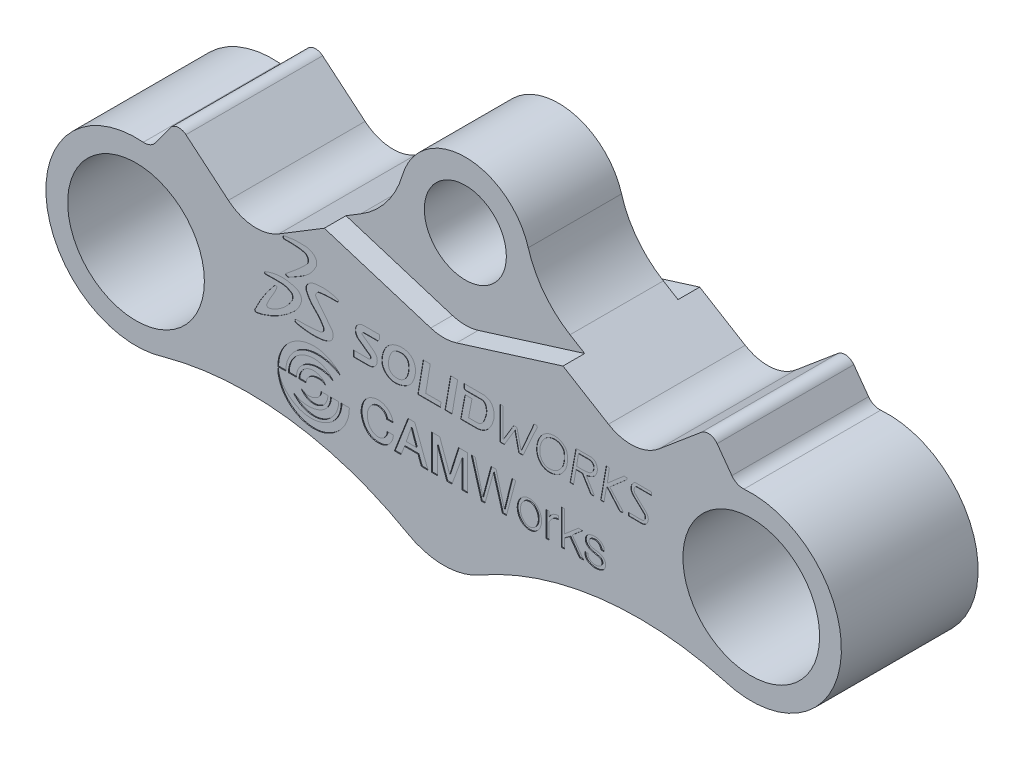
SolidWorks part; units mm, degrees
material "6061-T6 (SS)"
ref_plane "Front Plane" through (0, 0, 0) normal (0, 0, 1) x (1, 0, 0)
ref_plane "Top Plane" through (0, 0, 0) normal (0, 1, 0) x (1, 0, 0)
ref_plane "Right Plane" through (0, 0, 0) normal (1, 0, 0) x (0, 0, -1)
sketch "Sketch1" plane through (0, 0, 0) normal (0, 0, 1) x (1, 0, 0)
  line L0 (0, 0) -> (45, 7.9347) construction
  line L1 (0, 0) -> (0, 30) construction
  line L2 (0, 0) -> (0, -25.1431) construction
  line L3 (0, 0) -> (113.4618, 0) construction
  line L4 (45, 7.9347) -> (34.3559, 20.6199) construction
  line L5 (45, 7.9347) -> (45, 35.6707) construction
  line L11 (39.0067, 26.2508) -> (42.1595, 21.8988)
  line L13 (39.0067, 26.2508) -> (28.0029, 17.0175)
  line L14 (-45, 7.9347) -> (-34.3559, 20.6199) construction
  line L17 (28.0029, 17.0175) -> (15.3139, 24.7315)
  line L18 (0, 0) -> (-45, 7.9347) construction
  line L19 (-28.0029, 17.0175) -> (-15.3139, 24.7315)
  line L22 (-39.0067, 26.2508) -> (-28.0029, 17.0175)
  line L24 (-39.0067, 26.2508) -> (-42.1595, 21.8988)
  circle A0 centre (0, 30) radius 8 construction
  circle A2 centre (0, 0) radius 5.5562 construction
  circle A3 centre (45, 7.9347) radius 10 construction
  arc A5 (42.1595, 21.8988) -> (43.9399, 21.0787) centre (43.7791, 23.0722) ccw
  circle A7 centre (0, 30) radius 9.5875 construction
  arc A8 (10.5563, 0) -> (10.3959, 1.8331) centre (0, 0) ccw
  arc A9 (5.2476, -9.1596) -> (41.0161, -4.6357) centre (28.5656, -49.8611) cw
  arc A10 (9.2011, 32.6943) -> (-9.2011, 32.6943) centre (0, 30) ccw
  arc A11 (15.3139, 24.7315) -> (9.2011, 32.6943) centre (22.5268, 36.5963) cw
  arc A12 (41.0161, -4.6357) -> (43.9399, 21.0787) centre (45, 7.9347) ccw
  circle A13 centre (0, 0) radius 10.5563 construction
  arc A14 (-41.0161, -4.6357) -> (-43.9399, 21.0787) centre (-45, 7.9347) cw
  arc A15 (-15.3139, 24.7315) -> (-9.2011, 32.6943) centre (-22.5268, 36.5963) ccw
  arc A16 (-5.2476, -9.1596) -> (-41.0161, -4.6357) centre (-28.5656, -49.8611) ccw
  arc A19 (-42.1595, 21.8988) -> (-43.9399, 21.0787) centre (-43.7791, 23.0722) cw
  circle A21 centre (-45, 7.9347) radius 10 construction
  arc A22 (-5.2476, -9.1596) -> (5.2476, -9.1596) centre (0, 0) ccw
  point P26 (9.1088, 28.1848)
  point P35 (9.8679, 3.0169)
  dimension "D1" = 16
  dimension "D3" = 11.1125
  dimension "D6" = 20
  dimension "D12" = 2
  dimension "D4" = 45
  dimension "D5" = 30
  dimension "D7" = 10
  dimension "D8" = 40
  dimension "D16" = 5
  dimension "D17" = 1.5875
extrude "Boss-Extrude1" add sketch "Sketch1" along normal mid plane 20 contours A16 A22 A9 A12 A5 L11 A3 L13 L17 A11 A10 A15 L19 L22 A21 L24 A19 A14 A0 A2 region at (0, 10.4383, 0)
fillet "Fillet19" radius 6.35 2 edges at (28.0029, 17.0175, 0) (-28.0029, 17.0175, 0)
fillet "Fillet20" radius 1.5875 2 edges at (39.0067, 26.2508, 0) (-39.0067, 26.2508, 0)
sketch "Sketch2" plane through (0, 0, 10) normal (0, 0, 1) x (1, 0, 0)
  line L0 (11.5127, 28.1412) -> (22.6798, -3.324)
  line L1 (22.6798, -3.324) -> (47.5098, -15.7051)
  line L2 (47.5098, -15.7051) -> (71.0787, 26.7896)
  line L3 (71.0787, 26.7896) -> (23.8861, 37.9468)
  line L4 (23.8861, 37.9468) -> (11.5127, 28.1412)
  arc A0 (9.2011, 32.6943) -> (15.3139, 24.7315) centre (22.5268, 36.5963) ccw construction
  arc A1 (41.0161, -4.6357) -> (5.2476, -9.1596) centre (28.5656, -49.8611) ccw construction
sketch "Sketch3" plane through (0, 0, 10) normal (0, 0, 1) x (1, 0, 0)
  line L0 (0, 0) -> (0, 51.1761) construction
  line L1 (-13.039, 44.2465) -> (13.039, 44.2465)
  line L2 (13.039, 44.2465) -> (19.3473, 24.0178)
  line L3 (19.3473, 24.0178) -> (0, 17.9843)
  line L4 (-19.3473, 24.0178) -> (0, 17.9843)
  line L5 (-13.039, 44.2465) -> (-19.3473, 24.0178)
  point P9 (0, 44.2465)
extrude "Cut-Extrude2" cut sketch "Sketch3" against normal blind 3.175
fillet "Fillet9" radius 6.35 1 edges at (0, 17.9843, 8.4125)
mirror "Mirror13" about plane through (0, 0, 0) normal (0, 0, 1) of "Cut-Extrude2"
fillet "Fillet14" radius 6.35 1 edges at (0, 17.9843, -8.4125)
hole_wizard "Ø12.0mm Dowel Hole1" positions "Sketch11" profile "Sketch12" hole size "Ø12.0" standard "ANSI Metric" end condition through all
sketch "Sketch11" plane through (0, 0, 6.825) normal (0, 0, 1) x (1, 0, 0)
  point P0 (0, 30)
sketch "Sketch12" plane through (0, 30, 6.825) normal (1, 0, 0) x (0, -1, 0)
  line L0 (0, 0) -> (0, 16.825)
  line L1 (0, 16.825) -> (6, 16.825)
  line L2 (6, 16.825) -> (6, 0)
  line L5 (6, 0) -> (0, 0)
  line L11 (0, -6.35) -> (0, 107.95) construction
  dimension "Thru Hole Dia." = 12
  dimension "Thru Hole Depth" = 16.825
hole_wizard "Ø20.0mm Dowel Hole1" positions "Sketch13" profile "Sketch14" hole size "Ø20.0" standard "ANSI Metric" end condition through all
sketch "Sketch13" plane through (0, 0, 10) normal (0, 0, 1) x (1, 0, 0)
  point P0 (-45, 7.9347)
  point P3 (45, 7.9347)
sketch "Sketch14" plane through (-45, 7.9347, 10) normal (1, 0, 0) x (0, -1, 0)
  line L0 (0, 0) -> (0, 20)
  line L1 (0, 20) -> (10, 20)
  line L2 (10, 20) -> (10, 0)
  line L5 (10, 0) -> (0, 0)
  line L11 (0, -6.35) -> (0, 107.95) construction
  dimension "Thru Hole Dia." = 20
  dimension "Thru Hole Depth" = 20
sketch "Sketch19" plane through (0, 0, 10) normal (0, 0, 1) x (1, 0, 0)
  line L0 (0, 0) -> (0, 52.7084) construction
  circle A0 centre (45, 7.9347) radius 11.1125
  circle A1 centre (-45, 7.9347) radius 11.1125
  dimension "D1" = 22.225
sketch "Sketch20" plane through (0, 0, 10) normal (0, 0, 1) x (1, 0, 0)
  line L0 (-24.2613, 2.5064) -> (-23.1024, 2.5064)
  line L1 (-21.1371, 2.5064) -> (-20.1303, 2.5064)
  line L2 (-22.6988, 2.5064) -> (-21.5016, 2.5064)
  line L3 (-16.9282, 2.5064) -> (-17.96, 2.5064)
  line L4 (-15.4082, 2.5064) -> (-16.5618, 2.5064)
  line L5 (16.8161, 3.6153) -> (16.8161, 4.1275)
  line L6 (15.4419, 0.3486) -> (15.4419, 2.6934)
  line L7 (14.9756, 0.3486) -> (15.4419, 0.3486)
  line L8 (14.9756, 4.0314) -> (14.9756, 0.3486)
  line L9 (15.4419, 4.0314) -> (14.9756, 4.0314)
  line L10 (15.4419, 3.3134) -> (15.4419, 4.0314)
  line L11 (23.0367, 2.9061) -> (23.4912, 2.9061)
  line L12 (21.1196, 1.5282) -> (20.6711, 1.5282)
  line L24 (-8.3465, 3.7921) -> (-7.4097, 3.7921)
  line L25 (-7.3744, 2.2787) -> (-8.2537, 2.2787)
  line L26 (2.6811, 4.3434) -> (2.6811, 0.3486)
  line L27 (2.6811, 0.3486) -> (3.4934, 0.3486)
  line L28 (3.4934, 0.3486) -> (3.4934, 5.4578)
  line L29 (3.4934, 5.4578) -> (2.1789, 5.4578)
  line L30 (2.1789, 5.4578) -> (0.8894, 1.4078)
  line L31 (0.8894, 1.4078) -> (-0.5714, 5.461)
  line L32 (-0.5714, 5.461) -> (-1.7638, 5.461)
  line L33 (-1.7638, 5.461) -> (-1.7638, 0.3486)
  line L34 (-1.7638, 0.3486) -> (-0.9199, 0.3486)
  line L35 (-0.9199, 0.3486) -> (-0.9199, 4.2121)
  line L36 (-0.9199, 4.2121) -> (0.4726, 0.3486)
  line L37 (0.4726, 0.3486) -> (1.2108, 0.3486)
  line L38 (1.2108, 0.3486) -> (2.6811, 4.3434)
  line L39 (-4.7419, 4.5102) -> (-5.4681, 2.3913)
  line L40 (-3.9888, 2.3913) -> (-4.7419, 4.5102)
  line L41 (-5.4681, 2.3913) -> (-3.9888, 2.3913)
  line L42 (-24.2066, 2.489) -> (-24.2618, 2.489)
  line L43 (-13.8028, 2.5064) -> (-14.9977, 2.5064)
  line L44 (-5.7285, 1.6607) -> (-3.7553, 1.6607)
  line L45 (-6.2391, 0.3486) -> (-5.7285, 1.6607)
  line L46 (-7.2018, 0.3486) -> (-6.2391, 0.3486)
  line L47 (-5.212, 5.461) -> (-7.2018, 0.3486)
  line L48 (-4.2247, 5.461) -> (-5.212, 5.461)
  line L49 (-2.2957, 0.3486) -> (-4.2247, 5.461)
  line L50 (-3.2602, 0.3486) -> (-2.2957, 0.3486)
  line L51 (-3.7553, 1.6607) -> (-3.2602, 0.3486)
  line L52 (17.2152, 0.3486) -> (17.6916, 0.3486)
  line L53 (17.6916, 0.3486) -> (17.6916, 1.7618)
  line L54 (17.6916, 1.7618) -> (18.4695, 2.3165)
  line L55 (18.4695, 2.3165) -> (19.8729, 0.3486)
  line L56 (19.8729, 0.3486) -> (20.4853, 0.3486)
  line L57 (20.4853, 0.3486) -> (18.8132, 2.6934)
  line L58 (18.8132, 2.6934) -> (20.3356, 4.0074)
  line L59 (20.3356, 4.0074) -> (19.7018, 4.0074)
  line L60 (19.7018, 4.0074) -> (17.6916, 2.2723)
  line L61 (17.6916, 2.2723) -> (17.6916, 5.461)
  line L62 (17.6916, 5.461) -> (17.2152, 5.461)
  line L63 (17.2152, 5.461) -> (17.2152, 0.3486)
  line L64 (4.0328, 5.4578) -> (5.522, 0.3486)
  line L65 (5.522, 0.3486) -> (6.0506, 0.3486)
  line L66 (6.0506, 0.3486) -> (7.2887, 4.8318)
  line L67 (7.2887, 4.8318) -> (8.5954, 0.3486)
  line L68 (8.5954, 0.3486) -> (9.1816, 0.3486)
  line L69 (9.1816, 0.3486) -> (10.5463, 5.461)
  line L70 (10.5463, 5.461) -> (10.0007, 5.461)
  line L71 (10.0007, 5.461) -> (8.8885, 0.9778)
  line L72 (8.8885, 0.9778) -> (7.6674, 5.461)
  line L73 (7.6674, 5.461) -> (6.934, 5.461)
  line L74 (6.934, 5.461) -> (5.7373, 0.9778)
  line L75 (5.7373, 0.9778) -> (4.6136, 5.4578)
  line L76 (4.6136, 5.4578) -> (4.0328, 5.4578)
  ellipse E0 centre (12.5441, 2.204) end of major axis (12.4598, 0.1977) minor radius 1.779
  ellipse E1 centre (12.5441, 2.204) end of major axis (12.5441, 3.7921) minor radius 1.3127
  spline S0 degree 3 poles (-23.1024, 2.5064) (-23.0971, 3.5859) (-22.4651, 5.2251) (-20.5491, 6.6301) (-18.078, 7.1112) (-16.1966, 6.6039) (-15.1548, 5.9628) knots 0 0 0 0 0.304367 0.466255 0.655371 1 1 1 1
  spline S1 degree 3 poles (-15.1548, 5.9628) (-15.5783, 6.5498) (-16.8375, 7.4484) (-18.9616, 7.893) (-21.0692, 7.4482) (-23.4121, 5.9658) (-24.2655, 3.8586) (-24.2613, 2.5064) knots 0 0 0 0 0.172137 0.357725 0.501203 0.677746 1 1 1 1
  spline S2 degree 3 poles (-20.1303, 2.5064) (-20.1324, 2.9593) (-19.6326, 3.6975) (-18.3871, 4.0366) (-17.5768, 3.8704) (-17.2458, 3.5736) knots 0 0 0 0 0.355167 0.653312 1 1 1 1
  spline S3 degree 3 poles (-17.2458, 3.5736) (-17.4055, 3.9058) (-17.9769, 4.444) (-19.1021, 4.7031) (-20.5335, 4.2616) (-21.1665, 3.2292) (-21.1371, 2.5064) knots 0 0 0 0 0.202687 0.415279 0.607942 1 1 1 1
  spline S4 degree 3 poles (-21.5016, 2.5064) (-21.5879, 3.3398) (-20.8524, 4.5882) (-19.1216, 5.3) (-17.5419, 5.3116) (-16.5539, 4.9658) (-16.1028, 4.6737) knots 0 0 0 0 0.336822 0.562344 0.770945 1 1 1 1
  spline S5 degree 3 poles (-16.1028, 4.6737) (-16.6594, 5.4446) (-18.0791, 6.3254) (-20.166, 6.0885) (-22.0368, 5.0527) (-22.7154, 3.5249) (-22.6988, 2.5064) knots 0 0 0 0 0.313136 0.502366 0.666444 1 1 1 1
  spline S6 degree 3 poles (-17.96, 2.5064) (-17.932, 1.8223) (-19.0083, 0.9185) (-20.3256, 1.0433) (-20.8296, 1.4355) knots 0 0 0 0 0.499578 1 1 1 1
  spline S7 degree 3 poles (-20.8296, 1.4355) (-20.5724, 0.9811) (-19.817, 0.3947) (-18.5061, 0.3779) (-17.3016, 1.0011) (-16.9361, 1.9615) (-16.9282, 2.5064) knots 0 0 0 0 0.287736 0.487574 0.695315 1 1 1 1
  spline S8 degree 3 poles (-16.5618, 2.5064) (-16.5115, 1.8371) (-16.9702, 0.6799) (-18.4014, -0.1179) (-20.0813, -0.4016) (-21.3098, -0.08) (-21.9604, 0.3429) knots 0 0 0 0 0.283056 0.482539 0.671248 1 1 1 1
  spline S9 degree 3 poles (-21.9604, 0.3429) (-21.5349, -0.3362) (-20.3963, -1.0126) (-18.5359, -1.271) (-16.9531, -0.6568) (-15.733, 0.6766) (-15.316, 1.8629) (-15.4082, 2.5064) knots 0 0 0 0 0.257455 0.416875 0.60526 0.789878 1 1 1 1
  spline S10 degree 3 poles (15.4419, 2.6934) (15.602, 2.9028) (15.8927, 3.463) (16.5054, 3.6094) (16.8161, 3.6153) knots 0 0 0 0 0.469307 1 1 1 1
  spline S11 degree 3 poles (16.8161, 4.1275) (16.2755, 4.1602) (15.6912, 3.8377) (15.4419, 3.3134) knots 0 0 0 0 1 1 1 1
  spline S12 degree 3 poles (23.4912, 2.9061) (23.5069, 3.3021) (23.4377, 3.5745) (22.8174, 4.1301) (22.0633, 4.2006) (21.4391, 4.1124) (20.7962, 3.6676) (20.6048, 2.8681) (21.4202, 2.0292) (22.2991, 2.0194) (23.1045, 1.7199) (23.2793, 1.0222) (22.5578, 0.5504) (21.6195, 0.5811) (21.0009, 1.1205) (21.1196, 1.5282) knots 0 0 0 0 0.067062 0.148975 0.20304 0.28682 0.328691 0.4252 0.488568 0.640215 0.674333 0.728187 0.813903 0.886703 1 1 1 1
  spline S13 degree 3 poles (20.6711, 1.5282) (20.614, 1.2217) (20.7979, 0.6477) (21.6707, 0.1651) (22.6282, 0.1318) (23.6557, 0.6248) (23.8047, 1.6699) (23.0039, 2.4509) (22.1415, 2.4551) (21.281, 2.7015) (21.2066, 3.5303) (21.8459, 3.7244) (22.6106, 3.789) (23.0273, 3.129) (23.0367, 2.9061) knots 0 0 0 0 0.091071 0.156874 0.280395 0.364886 0.466496 0.536468 0.665479 0.716573 0.778128 0.84612 0.890812 1 1 1 1
  spline S14 degree 3 poles (-7.4097, 3.7921) (-7.4612, 4.6654) (-8.603, 5.7637) (-10.3346, 5.5952) (-11.6171, 4.8127) (-12.1965, 3.3447) (-11.9341, 1.6356) (-11.0709, 0.4637) (-9.6771, 0.0852) (-8.2935, 0.3052) (-7.4939, 1.3895) (-7.3516, 2.0564) (-7.3744, 2.2787) knots 0 0 0 0 0.175331 0.271237 0.33858 0.47311 0.570736 0.688741 0.747217 0.858562 0.957457 1 1 1 1
  spline S15 degree 3 poles (-8.2537, 2.2787) (-8.2617, 1.7264) (-8.8948, 0.8033) (-10.1462, 0.9543) (-10.8222, 1.5142) (-11.2318, 2.5289) (-11.1606, 3.8265) (-10.1272, 4.9836) (-8.7838, 4.7625) (-8.3631, 4.0824) (-8.3465, 3.7921) knots 0 0 0 0 0.179682 0.286073 0.363963 0.452172 0.627882 0.757863 0.910918 1 1 1 1
  spline S16 degree 3 poles (-14.9977, 2.5064) (-14.9865, 1.5454) (-15.7297, -0.601) (-18.5104, -1.765) (-21.465, -1.4226) (-23.6002, 0.1837) (-24.1678, 1.9265) (-24.2066, 2.489) knots 0.001261 0.001261 0.001261 0.001261 0.216474 0.470316 0.597834 0.876936 1 1 1 1
  spline S17 degree 3 poles (-24.2618, 2.489) (-24.2696, 2.2031) (-24.2186, 1.4078) (-23.8399, 0.2067) (-22.8245, -1.2742) (-20.9046, -2.6451) (-18.1716, -2.9286) (-16.0515, -1.8894) (-14.3277, -0.2242) (-13.7779, 1.416) (-13.8028, 2.5064) knots 0 0 0 0 0.052567 0.145511 0.227179 0.378978 0.564372 0.699238 0.800017 0.99894 0.99894 0.99894 0.99894
extrude "Cut-Extrude7" cut sketch "Sketch20" against normal blind 0.127 contours L42 S17 L43 S16 | S8 S9 L4 | S6 S7 L3 | S2 S3 L1 | S4 S5 L2 | S0 S1 L0 | L25 S15 L24 S14 | L44 L51 L50 L49 L48 L47 L46 L45 L41 L39 L40 | L75 L76 L64 L65 L66 L67 L68 L69 L70 L71 L72 L73 L74 | E0 E1 | L5 S11 L10 L9 L8 L7 L6 S10 | L62 L63 L52 L53 L54 L55 L56 L57 L58 L59 L60 L61 | L12 S13 L11 S12 | L35 L36 L37 L38 L26 L27 L28 L29 L30 L31 L32 L33 L34 region at (-20.848, 7.292, 10) region at (-19.6828, 3.707, 10) region at (-20.3183, 4.7343, 10) region at (-18.3829, 1.3043, 10) region at (-17.9104, -0.9069, 10) region at (15.9644, 3.4053, 10) region at (22.1946, 2.1781, 10) region at (-11.2259, 2.7056, 10) region at (-19.4824, -1.7214, 10) region at (-6.0498, 1.0303, 10) region at (18.3267, 2.5398, 10) region at (4.3232, 5.375, 10) region at (12.6262, 4.1567, 10)
sketch "Sketch22" plane through (0, 0, 10) normal (0, 0, 1) x (1, 0, 0)
  line L0 (128.642, -102.015) -> (744.642, -102.015) construction
  line L1 (-2.9817, 13.981) -> (-3.772, 9.2249)
  line L2 (-3.772, 9.2249) -> (-0.4945, 9.2249)
  line L3 (-0.4945, 9.2249) -> (-0.3768, 9.9328)
  line L4 (-0.3768, 9.9328) -> (-2.6267, 9.9328)
  line L5 (-2.6267, 9.9328) -> (-1.954, 13.981)
  line L6 (-1.954, 13.981) -> (-2.9817, 13.981)
  line L7 (1.0211, 13.981) -> (2.0499, 13.981)
  line L8 (2.0499, 13.981) -> (1.2305, 9.2249)
  line L9 (1.2305, 9.2249) -> (0.2017, 9.2249)
  line L10 (0.2017, 9.2249) -> (1.0211, 13.981)
  line L11 (3.1314, 12.6346) -> (4.1476, 12.6346)
  line L12 (4.1476, 12.6346) -> (3.6475, 9.9687)
  line L13 (3.6475, 9.9687) -> (4.831, 9.9687)
  line L14 (-9.4112, 13.981) -> (-11.7339, 13.981)
  line L15 (-13.1933, 10.13) -> (-10.9089, 10.13)
  line L16 (-13.1933, 10.13) -> (-13.1933, 9.2599)
  line L17 (-13.1933, 9.2599) -> (-10.9525, 9.2599)
  line L18 (-12.4337, 11.8297) -> (-10.788, 10.6322)
  line L19 (-10.2413, 11.5241) -> (-11.8393, 12.6869)
  line L20 (-11.7836, 13.0429) -> (-9.652, 13.0429)
  line L21 (-9.652, 13.0429) -> (-9.4112, 13.3557)
  line L22 (-9.4112, 13.3557) -> (-9.4112, 13.981)
  line L23 (3.1314, 12.6346) -> (2.4906, 9.2182)
  line L24 (2.4906, 9.2182) -> (4.7833, 9.2182)
  line L25 (5.7029, 13.981) -> (2.9784, 13.981)
  line L26 (3.2614, 13.2046) -> (5.5148, 13.2046)
  line L27 (8.2456, 13.981) -> (8.2456, 9.1881)
  line L28 (8.2456, 9.1881) -> (8.8753, 9.1881)
  line L29 (8.8753, 9.1881) -> (10.4222, 11.7688)
  line L30 (10.4222, 11.7688) -> (10.9975, 9.1881)
  line L31 (10.9975, 9.1881) -> (11.6038, 9.1881)
  line L32 (11.6038, 9.1881) -> (13.7013, 13.7935)
  line L33 (13.7013, 13.7935) -> (13.6595, 13.981)
  line L34 (13.6595, 13.981) -> (13.2328, 13.981)
  line L35 (13.2328, 13.981) -> (11.3894, 9.7227)
  line L36 (11.3894, 9.7227) -> (11.3007, 9.7227)
  line L37 (11.3007, 9.7227) -> (10.7305, 12.2808)
  line L38 (10.7305, 12.2808) -> (10.245, 12.2808)
  line L39 (10.245, 12.2808) -> (8.7639, 9.81)
  line L40 (8.7639, 9.81) -> (8.6704, 9.81)
  line L41 (8.6704, 9.81) -> (8.7172, 13.981)
  line L42 (8.7172, 13.981) -> (8.2456, 13.981)
  line L43 (19.3559, 13.9497) -> (18.4979, 9.1881)
  line L44 (18.4979, 9.1881) -> (19.0009, 9.1881)
  line L45 (19.0009, 9.1881) -> (19.3711, 11.2425)
  line L46 (19.3711, 11.2425) -> (20.2877, 11.2425)
  line L47 (20.2877, 11.2425) -> (21.5443, 9.1881)
  line L48 (21.5443, 9.1881) -> (21.8765, 9.1881)
  line L49 (21.8765, 9.1881) -> (21.9714, 9.2599)
  line L50 (21.9714, 9.2599) -> (21.9714, 9.4455)
  line L51 (21.9714, 9.4455) -> (20.9322, 11.1444)
  line L52 (19.3559, 13.9497) -> (21.493, 13.9497)
  line L53 (20.9322, 11.2816) -> (20.9322, 11.1444)
  line L54 (19.7193, 13.4693) -> (19.455, 11.7225)
  line L55 (19.455, 11.7225) -> (20.3274, 11.7225)
  line L56 (19.7193, 13.4693) -> (21.3007, 13.4693)
  line L57 (23.7899, 13.9497) -> (22.9678, 9.1881)
  line L58 (22.9678, 9.1881) -> (23.4569, 9.1881)
  line L59 (23.4569, 9.1881) -> (23.8184, 11.2816)
  line L60 (23.8184, 11.2816) -> (23.946, 11.2816)
  line L61 (23.946, 11.2816) -> (25.767, 9.1881)
  line L62 (25.767, 9.1881) -> (26.1625, 9.1881)
  line L63 (26.1625, 9.1881) -> (26.2605, 9.3813)
  line L64 (26.2605, 9.3813) -> (24.2974, 11.5266)
  line L65 (24.2974, 11.5266) -> (26.8031, 13.7009)
  line L66 (26.8031, 13.7009) -> (26.8031, 13.9497)
  line L67 (26.8031, 13.9497) -> (26.3865, 13.9497)
  line L68 (26.3865, 13.9497) -> (23.946, 11.832)
  line L69 (23.946, 11.832) -> (24.2344, 13.8253)
  line L70 (24.2344, 13.8253) -> (24.1265, 13.9497)
  line L71 (24.1265, 13.9497) -> (23.7899, 13.9497)
  line L72 (30.4315, 13.9497) -> (28.1771, 13.9497)
  line L73 (27.7505, 12.1488) -> (29.2938, 10.682)
  line L74 (28.9432, 9.6786) -> (27.0483, 9.6964)
  line L75 (30.4315, 13.4925) -> (28.1771, 13.4925)
  line L76 (28.0655, 12.4802) -> (29.6088, 11.0134)
  line L77 (28.9388, 9.2214) -> (27.044, 9.2392)
  line L78 (30.4315, 13.9497) -> (30.4315, 13.4925)
  line L79 (27.0483, 9.6964) -> (27.044, 9.2392)
  line L80 (-23.039, 14.9078) -> (-21.8627, 15.8733)
  line L81 (2.9784, 13.3941) -> (2.9784, 13.981)
  arc A0 (-11.8393, 12.6869) -> (-11.7836, 13.0429) centre (-11.7201, 12.8506) cw
  arc A1 (-11.7339, 13.981) -> (-12.4337, 11.8297) centre (-11.7339, 12.7915) ccw
  arc A2 (-10.788, 10.6322) -> (-10.9089, 10.13) centre (-10.9525, 10.4061) cw
  arc A3 (-10.9525, 9.2599) -> (-10.2413, 11.5241) centre (-10.9525, 10.5037) ccw
  arc A4 (4.7833, 9.2182) -> (6.7117, 10.2158) centre (4.7833, 11.5808) ccw
  arc A5 (6.7117, 10.2158) -> (7.3259, 11.5671) centre (3.4936, 12.4937) ccw
  arc A6 (7.3259, 11.5671) -> (7.1901, 13.1196) centre (4.9502, 12.1415) ccw
  arc A7 (7.1901, 13.1196) -> (6.3859, 13.8651) centre (5.9338, 12.571) ccw
  arc A8 (6.3859, 13.8651) -> (5.7029, 13.981) centre (5.7029, 11.9102) ccw
  arc A9 (5.5148, 13.2046) -> (6.1315, 12.7825) centre (5.5148, 12.5431) cw
  arc A10 (6.1315, 12.7825) -> (6.2047, 11.6047) centre (4.3188, 12.0787) cw
  arc A11 (6.2047, 11.6047) -> (5.8719, 10.6917) centre (1.6368, 12.7527) cw
  arc A12 (4.831, 9.9687) -> (5.8719, 10.6917) centre (4.831, 11.0795) ccw
  arc A13 (-24.7542, 12.5152) -> (-27.6149, 8.0822) centre (-11.0495, 0.5318) ccw
  arc A14 (-27.6149, 8.0822) -> (-27.3909, 7.7836) centre (-27.4214, 7.994) ccw
  arc A15 (-27.3909, 7.7836) -> (-26.4475, 7.994) centre (-28.3136, 14.1415) ccw
  arc A16 (-26.4475, 7.994) -> (-21.8071, 10.7493) centre (-29.7299, 18.8073) ccw
  arc A17 (-21.8071, 10.7493) -> (-20.8263, 12.3784) centre (-24.4815, 13.4693) ccw
  arc A18 (-20.8263, 12.3784) -> (-20.8773, 13.1196) centre (-21.8402, 12.681) ccw
  arc A19 (-20.8773, 13.1196) -> (-21.634, 13.7838) centre (-21.9932, 12.6113) ccw
  arc A20 (-21.634, 13.7838) -> (-22.2572, 13.9543) centre (-24.7753, 3.5301) ccw
  arc A21 (-22.2572, 13.9543) -> (-25.6583, 13.7733) centre (-23.6547, 8.1691) ccw
  arc A22 (-25.6583, 13.7733) -> (-26.1478, 13.5938) centre (-14.8129, -16.5622) ccw
  arc A23 (-26.1478, 13.5938) -> (-26.1547, 13.3557) centre (-26.1025, 13.4734) ccw
  arc A24 (-26.1547, 13.3557) -> (-25.8123, 13.2928) centre (-25.8522, 14.0385) ccw
  arc A25 (-25.8123, 13.2928) -> (-23.6606, 13.2927) centre (-24.7367, -6.81) cw
  arc A26 (-23.6606, 13.2927) -> (-22.6962, 13.0429) centre (-23.7947, 10.7887) cw
  arc A27 (-22.6962, 13.0429) -> (-22.3206, 12.8506) centre (-27.3882, 3.4145) cw
  arc A28 (-22.3206, 12.8506) -> (-22.1349, 12.6238) centre (-22.5021, 12.5127) cw
  arc A29 (-22.1349, 12.6238) -> (-22.2316, 11.8297) centre (-23.0846, 12.3365) cw
  arc A30 (-22.2316, 11.8297) -> (-25.1553, 9.3724) centre (-27.2147, 14.7906) cw
  arc A31 (-25.1553, 9.3724) -> (-25.6483, 9.259) centre (-25.813, 11.1029) cw
  arc A32 (-25.6483, 9.259) -> (-25.8683, 9.5496) centre (-25.6674, 9.4731) cw
  arc A33 (-24.7542, 12.5152) -> (-24.4831, 12.6067) centre (-24.5401, 12.328) cw
  arc A34 (-24.4831, 12.6067) -> (-24.3969, 12.4524) centre (-24.5065, 12.4924) cw
  arc A35 (-24.3969, 12.4524) -> (-25.0673, 11.1029) centre (-30.7594, 14.7718) cw
  arc A36 (-25.0673, 11.1029) -> (-25.8683, 9.5496) centre (-17.4402, 6.1867) ccw
  arc A37 (15.5711, 13.3941) -> (16.8835, 13.3941) centre (16.2273, 11.5266) cw
  arc A38 (15.5711, 13.3941) -> (14.5077, 12.5431) centre (16.254, 11.4508) ccw
  arc A39 (14.5077, 12.5431) -> (14.1532, 11.7225) centre (17.0241, 10.9691) ccw
  arc A40 (14.1532, 11.7225) -> (14.0724, 10.7493) centre (16.8851, 11.0056) ccw
  arc A41 (14.0724, 10.7493) -> (14.5901, 9.7227) centre (15.6306, 10.8913) ccw
  arc A42 (14.5901, 9.7227) -> (15.1733, 9.4455) centre (15.3569, 10.5839) ccw
  arc A43 (15.1733, 9.4455) -> (16.9255, 10.0368) centre (15.4889, 11.4023) ccw
  arc A44 (16.9255, 10.0368) -> (17.2922, 10.5037) centre (14.6392, 12.2098) ccw
  arc A45 (17.2922, 10.5037) -> (17.5668, 11.1512) centre (15.5481, 11.6253) ccw
  arc A46 (17.5668, 11.1512) -> (17.6213, 12.5431) centre (14.0045, 11.9879) ccw
  arc A47 (17.6213, 12.5431) -> (17.3551, 13.0623) centre (16.7088, 12.403) ccw
  arc A48 (17.3551, 13.0623) -> (16.8835, 13.3941) centre (16.1062, 11.7884) ccw
  arc A49 (18.0118, 11.0466) -> (18.0732, 12.6124) centre (14.0045, 11.9879) ccw
  arc A50 (18.0732, 12.6124) -> (17.6751, 13.3888) centre (16.7088, 12.403) ccw
  arc A51 (17.6751, 13.3888) -> (17.0593, 13.8168) centre (16.1062, 11.7884) ccw
  arc A52 (15.4196, 13.8254) -> (17.0593, 13.8168) centre (16.2273, 11.5266) cw
  arc A53 (15.4196, 13.8254) -> (14.1201, 12.7855) centre (16.254, 11.4508) ccw
  arc A54 (14.1201, 12.7855) -> (13.711, 11.8386) centre (17.0241, 10.9691) ccw
  arc A55 (13.711, 11.8386) -> (13.6171, 10.7078) centre (16.8851, 11.0056) ccw
  arc A56 (13.6171, 10.7078) -> (14.2861, 9.3813) centre (15.6306, 10.8913) ccw
  arc A57 (14.2861, 9.3813) -> (15.1005, 8.9942) centre (15.3569, 10.5839) ccw
  arc A58 (15.1005, 8.9942) -> (17.2569, 9.7219) centre (15.4889, 11.4023) ccw
  arc A59 (17.2569, 9.7219) -> (17.6767, 10.2564) centre (14.6392, 12.2098) ccw
  arc A60 (17.6767, 10.2564) -> (18.0118, 11.0466) centre (15.5481, 11.6253) ccw
  arc A61 (21.493, 13.9497) -> (22.4136, 13.2776) centre (21.493, 12.983) cw
  arc A62 (22.4136, 13.2776) -> (21.7715, 11.5724) centre (21.0159, 12.8304) cw
  arc A63 (21.7715, 11.5724) -> (21.5625, 11.4649) centre (20.8526, 13.1024) cw
  arc A64 (21.5625, 11.4649) -> (20.9322, 11.2816) centre (20.5242, 13.8596) cw
  arc A65 (21.3007, 13.4693) -> (21.971, 12.8373) centre (21.3007, 12.7978) cw
  arc A66 (21.971, 12.8373) -> (21.9722, 12.8037) centre (21.2163, 12.7929) cw
  arc A67 (21.9722, 12.8037) -> (21.1243, 11.7884) centre (20.9578, 12.7892) cw
  arc A68 (21.1243, 11.7884) -> (20.3274, 11.7225) centre (20.3274, 16.5787) cw
  arc A69 (28.1771, 13.9497) -> (27.8237, 13.8261) centre (28.1771, 13.3826) ccw
  arc A70 (27.8237, 13.8261) -> (27.7505, 12.1488) centre (28.5173, 12.9556) ccw
  arc A71 (29.2938, 10.682) -> (29.3156, 9.8365) centre (28.8817, 10.2483) cw
  arc A72 (29.3156, 9.8365) -> (28.9432, 9.6786) centre (28.9479, 10.1855) cw
  arc A73 (28.1771, 13.4925) -> (28.1086, 13.4685) centre (28.1771, 13.3826) ccw
  arc A74 (28.1086, 13.4685) -> (28.0655, 12.4802) centre (28.5173, 12.9556) ccw
  arc A75 (29.6088, 11.0134) -> (29.6472, 9.5217) centre (28.8817, 10.2483) cw
  arc A76 (29.6472, 9.5217) -> (28.9388, 9.2214) centre (28.9479, 10.1855) cw
  arc A77 (-21.8627, 15.8733) -> (-20.0559, 17.5348) centre (-35.7156, 32.751) ccw
  arc A78 (-20.0559, 17.5348) -> (-20.1458, 18.7689) centre (-20.6497, 18.1118) ccw
  arc A79 (-20.1458, 18.7689) -> (-20.3126, 18.8549) centre (-20.4685, 18.348) ccw
  arc A80 (-20.3126, 18.8549) -> (-21.5028, 19.0669) centre (-21.7706, 14.1161) ccw
  arc A81 (-21.5028, 19.0669) -> (-23.2893, 19.1069) centre (-23.029, -9.1448) ccw
  arc A82 (-23.2893, 19.1069) -> (-23.3264, 19.1093) centre (-23.2917, 19.3676) cw
  arc A83 (-23.3264, 19.1093) -> (-23.3349, 19.5353) centre (-23.2977, 19.3229) cw
  arc A84 (-23.3349, 19.5353) -> (-22.1083, 19.7211) centre (-18.7653, -6.4934) cw
  arc A85 (-22.1083, 19.7211) -> (-21.4711, 19.7702) centre (-21.2997, 13.3808) cw
  arc A86 (-21.4711, 19.7702) -> (-20.2203, 19.7578) centre (-21.0137, 2.716) cw
  arc A87 (-20.2203, 19.7578) -> (-19.1699, 19.4261) centre (-20.2856, 17.722) cw
  arc A88 (-19.1699, 19.4261) -> (-18.8328, 19.1313) centre (-20.0559, 18.073) cw
  arc A89 (-18.8328, 19.1313) -> (-18.6816, 17.9053) centre (-19.6716, 18.4055) cw
  arc A90 (-18.6816, 17.9053) -> (-20.6807, 15.7438) centre (-23.4606, 20.3201) cw
  arc A91 (-20.6807, 15.7438) -> (-22.6397, 14.6234) centre (-42.8948, 52.3124) cw
  arc A92 (-22.6397, 14.6234) -> (-23.0113, 14.6234) centre (-22.8255, 14.9691) cw
  arc A93 (-23.0113, 14.6234) -> (-23.039, 14.9078) centre (-22.9299, 14.7749) cw
  arc A94 (-15.662, 15.4646) -> (-18.9306, 15.6747) centre (-17.7046, 9.2189) ccw
  arc A95 (-18.9306, 15.6747) -> (-19.9811, 14.998) centre (-18.6199, 14.0385) ccw
  arc A96 (-19.9811, 14.998) -> (-20.0792, 14.1739) centre (-19.2678, 14.4952) ccw
  arc A97 (-20.0792, 14.1739) -> (-18.9547, 12.5127) centre (-15.7672, 15.8816) ccw
  arc A98 (-18.9547, 12.5127) -> (-17.6241, 10.8511) centre (-24.2789, 6.8855) cw
  arc A99 (-17.6241, 10.8511) -> (-17.6241, 10.2756) centre (-18.1069, 10.5634) cw
  arc A100 (-17.6241, 10.2756) -> (-18.0533, 9.9972) centre (-18.1211, 10.5719) cw
  arc A101 (-18.0533, 9.9972) -> (-21.5028, 9.8201) centre (-21.1129, 35.9111) cw
  arc A102 (-21.5028, 9.8201) -> (-21.737, 9.4455) centre (-21.5067, 9.5621) ccw
  arc A103 (-21.737, 9.4455) -> (-21.6459, 9.3737) centre (-21.6139, 9.5078) ccw
  arc A104 (-15.662, 15.4646) -> (-15.4208, 15.3316) centre (-15.8914, 14.7632) cw
  arc A105 (-15.4208, 15.3316) -> (-15.4208, 15.1131) centre (-15.5113, 15.2224) cw
  arc A106 (-15.4208, 15.1131) -> (-15.6754, 15.0269) centre (-15.661, 15.4032) cw
  arc A107 (-15.6754, 15.0269) -> (-18.1633, 14.9085) centre (-16.2314, 0.5157) ccw
  arc A108 (-18.1633, 14.9085) -> (-18.6816, 14.5037) centre (-18.0767, 14.2634) ccw
  arc A109 (-18.6816, 14.5037) -> (-18.6199, 14.0385) centre (-18.235, 14.3263) ccw
  arc A110 (-18.6199, 14.0385) -> (-16.4557, 11.2816) centre (41.0474, 58.6485) ccw
  arc A111 (-16.4557, 11.2816) -> (-16.287, 9.9463) centre (-17.4283, 10.4804) cw
  arc A112 (-16.287, 9.9463) -> (-16.6471, 9.5475) centre (-17.1192, 10.3358) cw
  arc A113 (-16.6471, 9.5475) -> (-17.8655, 9.1213) centre (-18.2912, 12.2928) cw
  arc A114 (-17.8655, 9.1213) -> (-20.2885, 9.1213) centre (-19.077, 18.1479) cw
  arc A115 (-20.2885, 9.1213) -> (-21.6459, 9.3737) centre (-18.4662, 22.6987) cw
  arc A116 (3.2614, 13.2046) -> (2.9784, 13.3941) centre (3.2614, 13.5107) cw
  spline S0 degree 3 poles (-5.9536, 13.2322) (-6.5483, 13.2327) (-7.227, 13.0857) (-7.6879, 12.5079) (-7.899, 12.003) (-8.0415, 11.4994) (-8.0515, 11.1444) (-8.0504, 10.8148) (-8.0359, 10.4022) (-7.7211, 9.968) (-7.0997, 9.7294) (-6.3705, 9.6988) (-5.5646, 10.2235) (-5.1198, 11.1786) (-5.0436, 12.1235) (-5.2688, 12.8444) (-5.6179, 13.0798) (-5.9536, 13.2322) (-6.5483, 13.2327) (-7.227, 13.0857) knots -0.106016 -0.074381 -0.037807 0 0.097808 0.150246 0.208882 0.257422 0.302122 0.311658 0.35279 0.422068 0.450225 0.5464 0.621192 0.717548 0.84255 0.893984 0.925619 0.962193 1 1.097808 1.150246 1.208882 only from (-6.3427, 13.2242) to (-6.3427, 13.2242)
  spline S1 degree 3 poles (-5.4548, 13.9527) (-6.5625, 14.0583) (-7.8379, 13.6062) (-8.6566, 12.5996) (-9.0236, 11.513) (-9.1323, 10.1885) (-8.3172, 9.3128) (-7.2611, 8.9285) (-6.1535, 9.0731) (-4.845, 9.7606) (-4.1562, 11.1054) (-4.023, 12.5446) (-4.6287, 13.5603) (-5.4548, 13.9527) (-6.5625, 14.0583) (-7.8379, 13.6062) knots -0.173121 -0.103505 -0.063598 0 0.108437 0.182277 0.243087 0.330527 0.425194 0.446033 0.547798 0.628437 0.724077 0.826879 0.896495 0.936402 1 1.108437 1.182277 1.243087 only from (-6.3272, 13.981) to (-6.3272, 13.981)
extrude "Cut-Extrude9" cut sketch "Sketch22" against normal blind 0.0508
